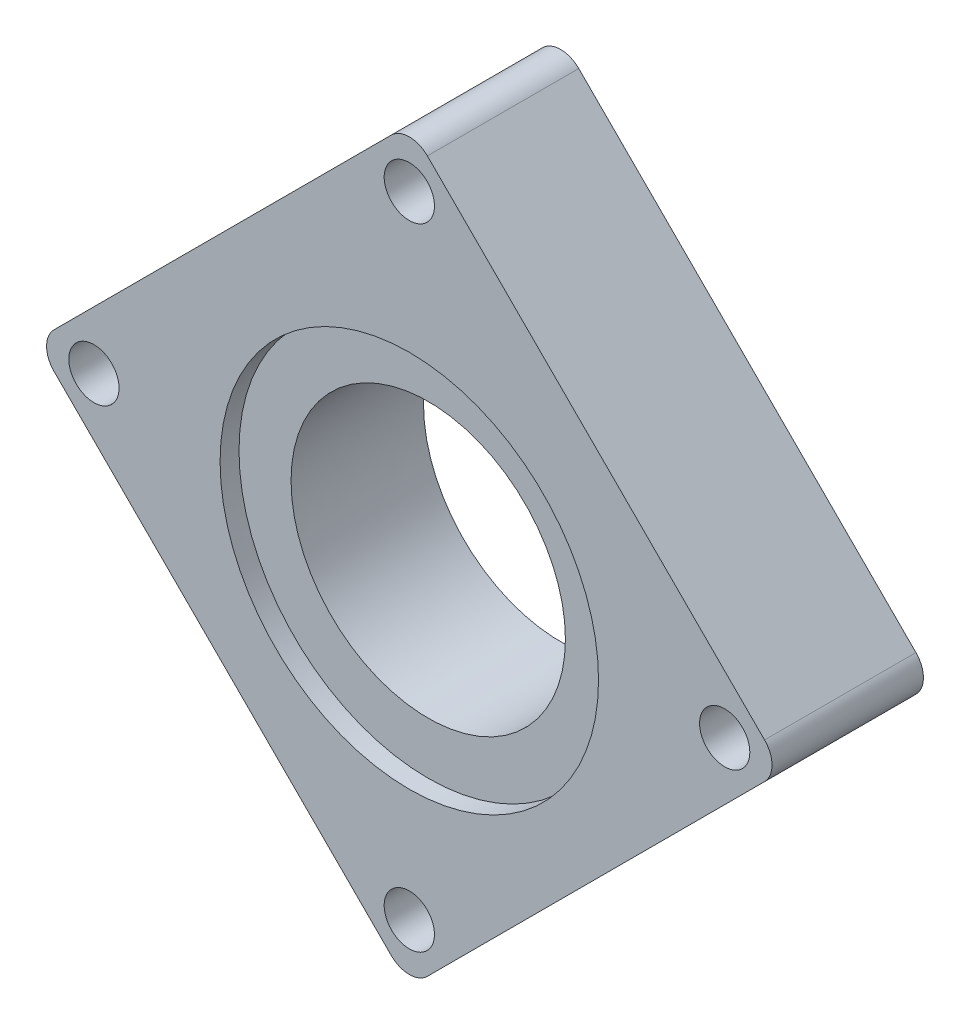
SolidWorks part; units mm, degrees
ref_plane "Front Plane" through (0, 0, 0) normal (0, 0, 1) x (1, 0, 0)
ref_plane "Top Plane" through (0, 0, 0) normal (0, 1, 0) x (1, 0, 0)
ref_plane "Right Plane" through (0, 0, 0) normal (1, 0, 0) x (0, 0, -1)
sketch "Sketch1" plane through (0, 0, 0) normal (0, 0, 1) x (1, 0, 0)
  line L48 (96.4567, 48.3669) -> (64.849, 79.9745)
  line L49 (92.4262, 40.518) -> (96.4567, 44.5485)
  line L52 (60.8185, 8.9103) -> (92.4262, 40.518)
  line L53 (52.9697, 12.9408) -> (57.0002, 8.9103)
  line L56 (21.362, 44.5485) -> (52.9697, 12.9408)
  line L57 (25.3925, 52.3974) -> (21.362, 48.3669)
  line L60 (57.0002, 84.0051) -> (25.3925, 52.3974)
  line L61 (64.849, 79.9745) -> (60.8185, 84.0051)
  circle A0 centre (58.9094, 45.0773) radius 14.5
  circle A12 centre (58.9094, 13.1247) radius 2.6556
  circle A13 centre (92.2424, 46.4577) radius 2.6556
  circle A14 centre (58.9094, 79.7907) radius 2.6556
  circle A15 centre (25.5763, 46.4577) radius 2.6556
  arc A31 (96.4567, 44.5485) -> (96.4567, 48.3669) centre (94.5475, 46.4577) ccw
  arc A33 (57.0002, 8.9103) -> (60.8185, 8.9103) centre (58.9094, 10.8195) ccw
  arc A35 (21.362, 48.3669) -> (21.362, 44.5485) centre (23.2712, 46.4577) ccw
  arc A37 (60.8185, 84.0051) -> (57.0002, 84.0051) centre (58.9094, 82.0959) ccw
  point P3 (25.5763, 46.4577)
  point P6 (58.9094, 13.1247)
  point P18 (92.2424, 46.4577)
  dimension "D1" = 29
extrude "Boss-Extrude1" add sketch "Sketch1" along normal blind 16
sketch "Sketch2" plane through (0, 0, 16) normal (0, 0, 1) x (1, 0, 0)
  circle A0 centre (58.9094, 45.0773) radius 20
extrude "Cut-Extrude1" cut sketch "Sketch2" against normal blind 2
